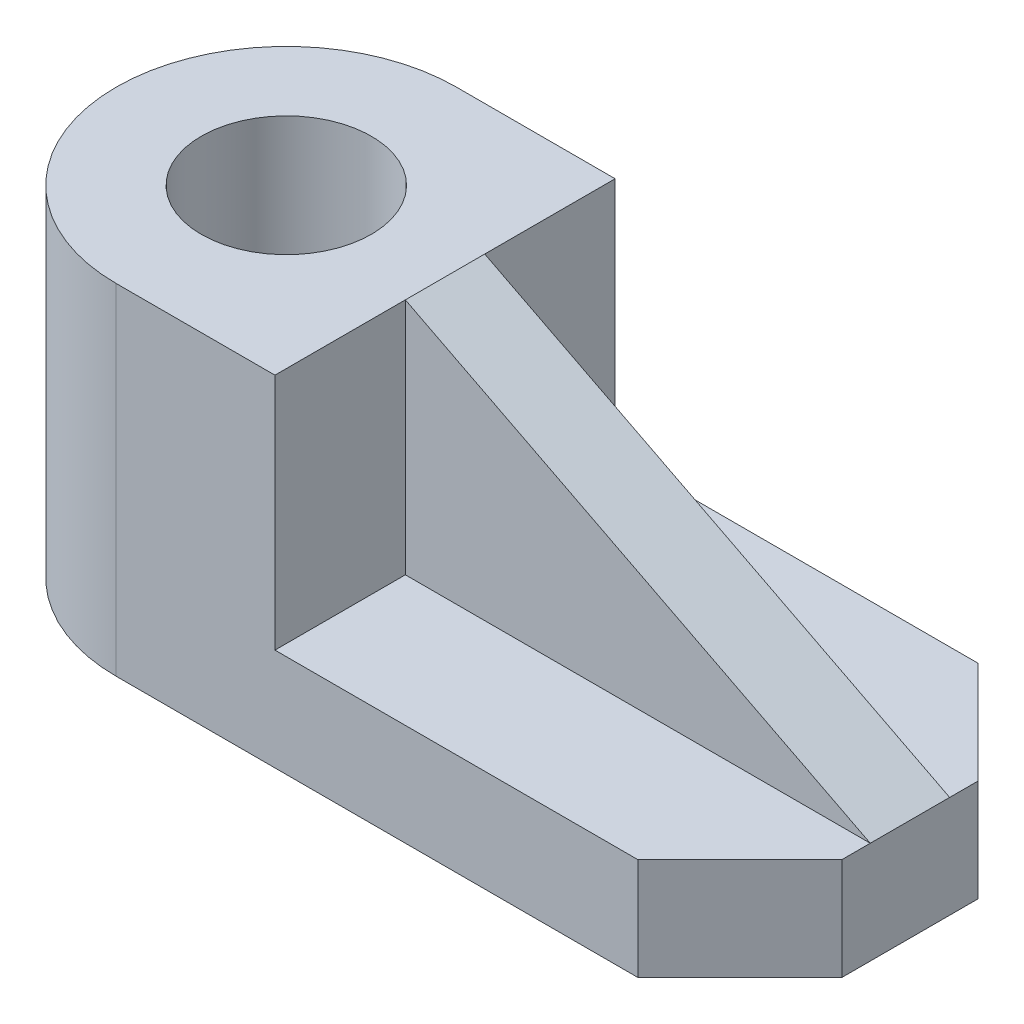
SolidWorks part; units mm, degrees
ref_plane "정면" through (0, 0, 0) normal (0, 0, 1) x (1, 0, 0)
ref_plane "윗면" through (0, 0, 0) normal (0, 1, 0) x (1, 0, 0)
ref_plane "우측면" through (0, 0, 0) normal (1, 0, 0) x (0, 0, -1)
sketch "스케치1" plane through (0, 0, 0) normal (0, 1, 0) x (1, 0, 0)
  line L0 (0, 0) -> (53.1429, 0) construction
  line L5 (14, -15) -> (0, -15)
  line L6 (14, -15) -> (14, 15)
  line L7 (14, 15) -> (0, 15)
  line L8 (0, -7.5) -> (0, 7.5)
  line L9 (14, 15) -> (46, 15)
  line L10 (14, -15) -> (46, -15)
  line L11 (55, -6) -> (55, 6)
  line L12 (46, -15) -> (55, -6)
  line L13 (46, 15) -> (55, 6)
  arc A0 (0, 15) -> (0, -15) centre (0, 0) ccw
  circle A1 centre (0, 0) radius 7.5
  point P17 (55, 0)
  dimension "D1" = 14
  dimension "D2" = 15
  dimension "D3" = 30
  dimension "D4" = 32
  dimension "D5" = 12
  dimension "D6" = 9
  dimension "D7" = 9
extrude "보스-돌출1" add sketch "스케치1" along normal blind 30 contours A1 L6 L7 A0 L5 region at (7, 0, 14.5827)
extrude "보스-돌출2" add sketch "스케치1<3>" along normal blind 9 contours L13 L9 L6 L10 L12 L11 region at (33.2663, 0, 0)
sketch "스케치1<3>" plane through (0, 0, 0) normal (0, 1, 0) x (1, 0, 0) same geometry as "스케치1"
sketch "스케치2" plane through (0, 0, 15) normal (0, 0, 1) x (1, 0, 0)
  line L0 (14, 30) -> (55, 9)
  line L1 (55, 9) -> (14, 9)
  line L2 (14, 9) -> (14, 30)
extrude "보스-돌출3" add sketch "스케치2" along normal mid plane 7 from offset 15 contours L2 L0 L1 offset against normal yes
